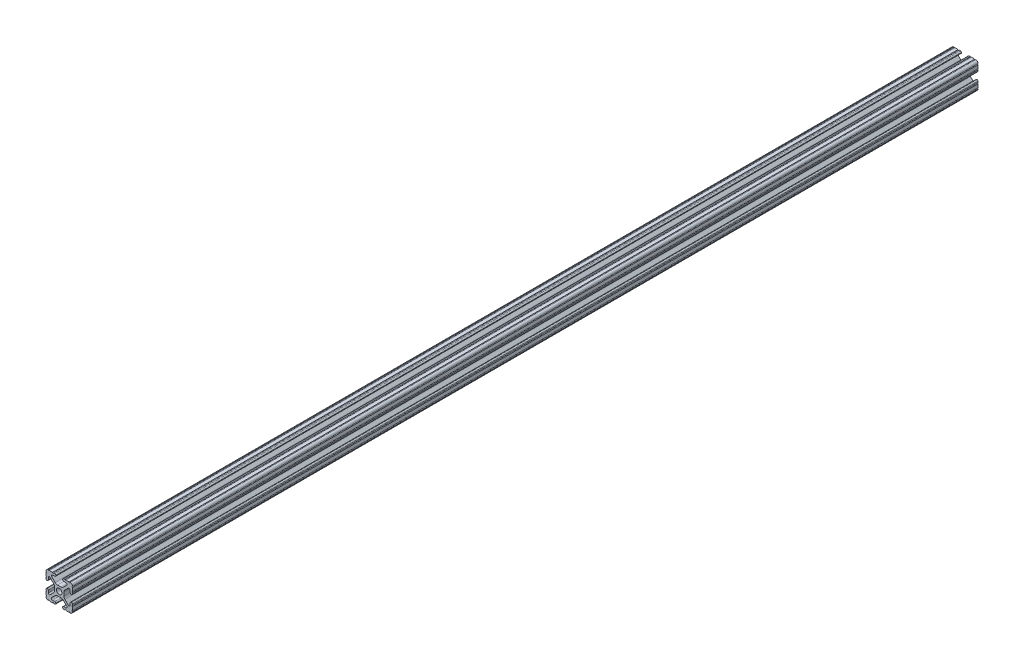
SolidWorks part; units mm, degrees
material "6063-T5"
ref_plane "Front Plane" through (0, 0, 0) normal (0, 0, 1) x (1, 0, 0)
ref_plane "Top Plane" through (0, 0, 0) normal (0, 1, 0) x (1, 0, 0)
ref_plane "Right Plane" through (0, 0, 0) normal (1, 0, 0) x (0, 0, -1)
sketch "Sketch1" plane through (0, 0, 0) normal (0, 0, 1) x (1, 0, 0)
  line L0 (-7.207, 8.7244) -> (-3.8983, 5.4232)
  line L1 (-4.2875, 10.4902) -> (-6.4768, 10.4902)
  line L2 (-3.2385, 11.651) -> (-3.2385, 11.5392)
  line L3 (-5.3171, 12.7) -> (-4.2875, 12.7)
  line L4 (0, 13.4005) -> (0, -14.8534) construction
  line L5 (12.7, 0) -> (-13.9989, 0) construction
  line L6 (-9.5504, 12.7) -> (-6.3331, 12.7)
  line L7 (-12.7, 6.3331) -> (-12.7, 9.5504)
  line L8 (-12.7, 4.2875) -> (-12.7, 5.3171)
  line L9 (-11.5392, 3.2385) -> (-11.651, 3.2385)
  line L10 (-10.4902, 6.4021) -> (-10.4902, 4.2875)
  line L11 (-5.441, 3.8408) -> (-8.7371, 7.1294)
  line L12 (-4.5085, -1.5932) -> (-4.5085, 1.5932)
  line L13 (-1.7093, -4.4958) -> (1.7093, -4.4958)
  line L14 (3.9523, -5.4237) -> (7.1797, -8.6452)
  line L15 (6.4164, -10.4902) -> (4.2875, -10.4902)
  line L16 (3.2385, -11.5392) -> (3.2385, -11.651)
  line L17 (4.2875, -12.7) -> (5.3171, -12.7)
  line L18 (6.3331, -12.7) -> (9.5504, -12.7)
  line L19 (12.7, -9.5504) -> (12.7, -6.3331)
  line L20 (12.7, -5.3171) -> (12.7, -4.2875)
  line L21 (11.651, -3.2385) -> (11.5392, -3.2385)
  line L22 (10.4902, -4.2875) -> (10.4902, -6.4021)
  line L23 (8.7371, -7.1294) -> (5.441, -3.8408)
  line L24 (4.5085, -1.5932) -> (4.5085, 1.5932)
  line L25 (5.441, 3.8408) -> (8.7371, 7.1294)
  line L26 (10.4902, 6.4021) -> (10.4902, 4.2875)
  line L27 (11.5392, 3.2385) -> (11.651, 3.2385)
  line L28 (12.7, 4.2875) -> (12.7, 5.3171)
  line L29 (12.7, 6.3331) -> (12.7, 9.5504)
  line L30 (9.5504, 12.7) -> (6.3331, 12.7)
  line L31 (5.3171, 12.7) -> (4.2875, 12.7)
  line L32 (3.2385, 11.651) -> (3.2385, 11.5392)
  line L33 (4.2875, 10.4902) -> (6.4768, 10.4902)
  line L34 (7.207, 8.7244) -> (3.8983, 5.4232)
  line L35 (1.6558, 4.4958) -> (-1.6558, 4.4958)
  line L36 (-8.7371, -7.1294) -> (-5.441, -3.8408)
  line L37 (-10.4902, -4.2875) -> (-10.4902, -6.4021)
  line L38 (-11.651, -3.2385) -> (-11.5392, -3.2385)
  line L39 (-12.7, -5.3171) -> (-12.7, -4.2875)
  line L40 (-12.7, -9.5504) -> (-12.7, -6.3331)
  line L41 (-6.3331, -12.7) -> (-9.5504, -12.7)
  line L42 (-4.2875, -12.7) -> (-5.3171, -12.7)
  line L43 (-3.2385, -11.5392) -> (-3.2385, -11.651)
  line L44 (-6.4164, -10.4902) -> (-4.2875, -10.4902)
  line L45 (-3.9523, -5.4237) -> (-7.1797, -8.6452)
  arc A0 (-7.207, 8.7244) -> (-6.4768, 10.4902) centre (-6.4768, 9.4563) cw
  arc A1 (-3.2385, 11.5392) -> (-4.2875, 10.4902) centre (-4.2875, 11.5392) cw
  arc A2 (-4.2875, 12.7) -> (-3.2385, 11.651) centre (-4.2875, 11.651) cw
  arc A3 (-5.3171, 12.7) -> (-6.3331, 12.7) centre (-5.8251, 12.7) cw
  arc A4 (-9.5504, 12.7) -> (-10.5664, 12.6998) centre (-10.0584, 12.7) cw
  arc A5 (-12.6998, 10.5664) -> (-10.5664, 12.6998) centre (-10.5918, 10.5918) cw
  arc A6 (-12.6998, 10.5664) -> (-12.7, 9.5504) centre (-12.7, 10.0584) cw
  arc A7 (-12.7, 6.3331) -> (-12.7, 5.3171) centre (-12.7, 5.8251) cw
  arc A8 (-11.651, 3.2385) -> (-12.7, 4.2875) centre (-11.651, 4.2875) cw
  arc A9 (-10.4902, 4.2875) -> (-11.5392, 3.2385) centre (-11.5392, 4.2875) cw
  circle A10 centre (0, 0) radius 2.6035
  arc A11 (-10.4902, 6.4021) -> (-8.7371, 7.1294) centre (-9.4628, 6.4021) cw
  arc A12 (-5.441, 3.8408) -> (-4.5085, 1.5932) centre (-7.6835, 1.5932) cw
  arc A13 (-4.5085, -1.5932) -> (-5.441, -3.8408) centre (-7.6835, -1.5932) cw
  arc A14 (-8.7371, -7.1294) -> (-10.4902, -6.4021) centre (-9.4628, -6.4021) cw
  arc A15 (-1.7093, -4.4958) -> (-3.9523, -5.4237) centre (-1.7093, -7.6708) ccw
  arc A16 (3.9523, -5.4237) -> (1.7093, -4.4958) centre (1.7093, -7.6708) ccw
  arc A17 (6.4164, -10.4902) -> (7.1797, -8.6452) centre (6.4164, -9.4098) ccw
  arc A18 (4.2875, -10.4902) -> (3.2385, -11.5392) centre (4.2875, -11.5392) ccw
  arc A19 (3.2385, -11.651) -> (4.2875, -12.7) centre (4.2875, -11.651) ccw
  arc A20 (6.3331, -12.7) -> (5.3171, -12.7) centre (5.8251, -12.7) ccw
  arc A21 (10.5664, -12.6998) -> (9.5504, -12.7) centre (10.0584, -12.7) ccw
  arc A22 (10.5664, -12.6998) -> (12.6998, -10.5664) centre (10.5918, -10.5918) ccw
  arc A23 (12.7, -9.5504) -> (12.6998, -10.5664) centre (12.7, -10.0584) ccw
  arc A24 (12.7, -5.3171) -> (12.7, -6.3331) centre (12.7, -5.8251) ccw
  arc A25 (12.7, -4.2875) -> (11.651, -3.2385) centre (11.651, -4.2875) ccw
  arc A26 (11.5392, -3.2385) -> (10.4902, -4.2875) centre (11.5392, -4.2875) ccw
  arc A27 (8.7371, -7.1294) -> (10.4902, -6.4021) centre (9.4628, -6.4021) ccw
  arc A28 (4.5085, -1.5932) -> (5.441, -3.8408) centre (7.6835, -1.5932) ccw
  arc A29 (5.441, 3.8408) -> (4.5085, 1.5932) centre (7.6835, 1.5932) ccw
  arc A30 (10.4902, 6.4021) -> (8.7371, 7.1294) centre (9.4628, 6.4021) ccw
  arc A31 (10.4902, 4.2875) -> (11.5392, 3.2385) centre (11.5392, 4.2875) ccw
  arc A32 (11.651, 3.2385) -> (12.7, 4.2875) centre (11.651, 4.2875) ccw
  arc A33 (12.7, 6.3331) -> (12.7, 5.3171) centre (12.7, 5.8251) ccw
  arc A34 (12.6998, 10.5664) -> (12.7, 9.5504) centre (12.7, 10.0584) ccw
  arc A35 (12.6998, 10.5664) -> (10.5664, 12.6998) centre (10.5918, 10.5918) ccw
  arc A36 (9.5504, 12.7) -> (10.5664, 12.6998) centre (10.0584, 12.7) ccw
  arc A37 (5.3171, 12.7) -> (6.3331, 12.7) centre (5.8251, 12.7) ccw
  arc A38 (4.2875, 12.7) -> (3.2385, 11.651) centre (4.2875, 11.651) ccw
  arc A39 (3.2385, 11.5392) -> (4.2875, 10.4902) centre (4.2875, 11.5392) ccw
  arc A40 (7.207, 8.7244) -> (6.4768, 10.4902) centre (6.4768, 9.4563) ccw
  arc A41 (1.6558, 4.4958) -> (3.8983, 5.4232) centre (1.6558, 7.6708) ccw
  arc A42 (-1.6558, 4.4958) -> (-3.8983, 5.4232) centre (-1.6558, 7.6708) cw
  arc A43 (-11.5392, -3.2385) -> (-10.4902, -4.2875) centre (-11.5392, -4.2875) cw
  arc A44 (-12.7, -4.2875) -> (-11.651, -3.2385) centre (-11.651, -4.2875) cw
  arc A45 (-12.7, -5.3171) -> (-12.7, -6.3331) centre (-12.7, -5.8251) cw
  arc A46 (-12.7, -9.5504) -> (-12.6998, -10.5664) centre (-12.7, -10.0584) cw
  arc A47 (-10.5664, -12.6998) -> (-12.6998, -10.5664) centre (-10.5918, -10.5918) cw
  arc A48 (-10.5664, -12.6998) -> (-9.5504, -12.7) centre (-10.0584, -12.7) cw
  arc A49 (-6.3331, -12.7) -> (-5.3171, -12.7) centre (-5.8251, -12.7) cw
  arc A50 (-3.2385, -11.651) -> (-4.2875, -12.7) centre (-4.2875, -11.651) cw
  arc A51 (-4.2875, -10.4902) -> (-3.2385, -11.5392) centre (-4.2875, -11.5392) cw
  arc A52 (-6.4164, -10.4902) -> (-7.1797, -8.6452) centre (-6.4164, -9.4098) cw
  dimension "D1" = 5.207
  dimension "D9" = 14.859
  dimension "D2" = 25.4
  dimension "D3" = 12.7
  dimension "D4" = 6.477
  dimension "D5" = 8.2042
  dimension "D6" = 9.017
  dimension "D8" = 2.2098
  dimension "D10" = 2.2098
extrude "Extrude1" add sketch "Sketch1" against normal blind 1219.2
sketch "Sketch2" plane through (0, 12.7, 0) normal (0, 1, 0) x (1, 0, 0)
  line L0 (20.849, 870) -> (-9.5504, 870) construction
  line L2 (-9.5504, 1219.2) -> (-9.5504, 0) construction
  line L4 (20.849, 870) -> (-46.7134, 870)
  line L5 (20.849, 870) -> (20.849, 1239.9082)
  line L6 (20.849, 1239.9082) -> (-46.7134, 1239.9082)
  line L7 (-46.7134, 870) -> (-46.7134, 1239.9082)
  dimension "D1" = 870
extrude "Cut-Extrude2" cut sketch "Sketch2" against normal through all
